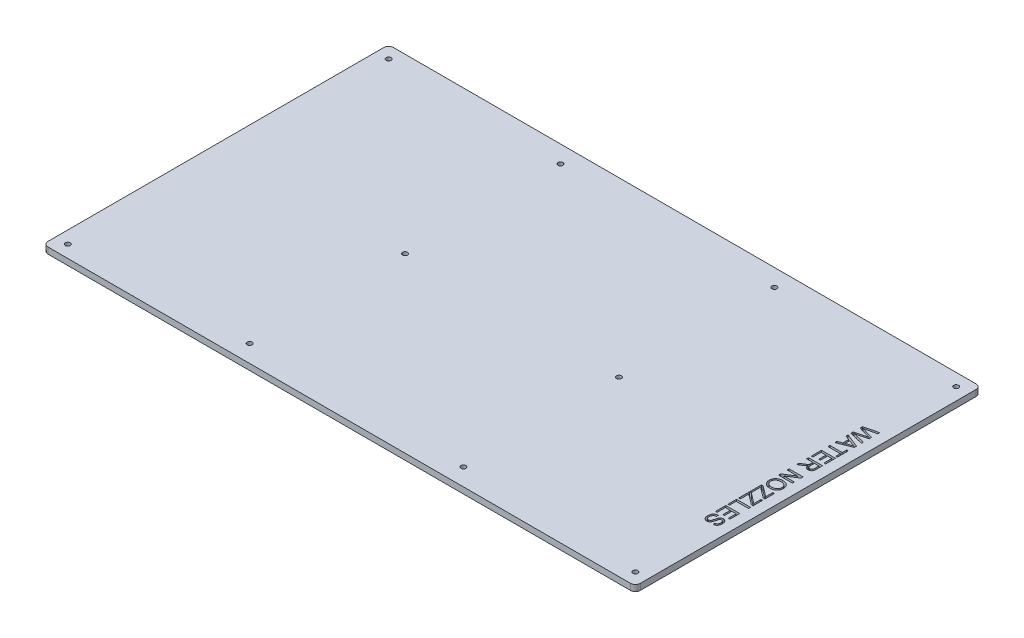
SolidWorks part; units mm, degrees
ref_plane "Front" through (0, 0, 0) normal (0, 0, 1) x (1, 0, 0)
ref_plane "Top" through (0, 0, 0) normal (0, 1, 0) x (1, 0, 0)
ref_plane "Right" through (0, 0, 0) normal (1, 0, 0) x (0, 0, -1)
sketch "Sketch1" plane through (0, 0, 0) normal (0, 1, 0) x (1, 0, 0)
  line L0 (139.7, 88.9) -> (139.7, -88.9) construction
  line L1 (-152.4, 88.9) -> (152.4, 88.9)
  line L2 (-152.4, 88.9) -> (-152.4, -88.9)
  line L3 (-152.4, -88.9) -> (152.4, -88.9)
  line L4 (152.4, 88.9) -> (152.4, -88.9)
  line L5 (-152.4, 88.9) -> (152.4, -88.9) construction
  line L6 (-152.4, -88.9) -> (152.4, 88.9) construction
  circle A0 centre (-55.0291, 80.01) radius 2.4574 construction
  circle A1 centre (-55.0291, 80.01) radius 2.4575 construction
  circle A2 centre (-55.0333, 0) radius 2.4574 construction
  circle A3 centre (-55.0333, 0) radius 2.4575 construction
  circle A4 centre (-55.0291, -80.01) radius 2.4574 construction
  circle A5 centre (-55.0291, -80.01) radius 2.4575 construction
  circle A6 centre (55.0291, -80.01) radius 2.4574 construction
  circle A7 centre (55.0291, -80.01) radius 2.4575 construction
  circle A8 centre (55.0333, 0) radius 2.4574 construction
  circle A9 centre (55.0333, 0) radius 2.4575 construction
  circle A10 centre (55.0291, 80.01) radius 2.4574 construction
  circle A11 centre (55.0291, 80.01) radius 2.4575 construction
  circle A12 centre (-55.0291, 80.01) radius 1.27
  circle A13 centre (-55.0333, 0) radius 1.27
  circle A14 centre (-55.0291, -80.01) radius 1.27
  circle A15 centre (55.0291, -80.01) radius 1.27
  circle A16 centre (55.0333, 0) radius 1.27
  circle A17 centre (55.0291, 80.01) radius 1.27
  circle A18 centre (-146.05, 82.55) radius 1.27
  circle A19 centre (-146.05, -82.55) radius 1.27
  circle A20 centre (146.05, -82.55) radius 1.27
  circle A21 centre (146.05, 82.55) radius 1.27
  point P0 (0, 0)
  dimension "D4" = 2.54
  dimension "D1" = 304.8
  dimension "D2" = 177.8
  dimension "D3" = 12.7
extrude "Boss-Extrude1" add sketch "Sketch1" along normal blind 3.175
sketch "Sketch2" plane through (0, 3.175, 0) normal (0, 1, 0) x (1, 0, 0)
  line L0 (139.7, 88.9) -> (139.7, -88.9) construction
  line L1 (152.4, 88.9) -> (-152.4, 88.9) construction
  line L2 (-152.4, -88.9) -> (152.4, -88.9) construction
  line L3 (152.4, -88.9) -> (152.4, 88.9) construction
  text T0 "WATER NOZZLES" font "Arial" height in points 28
  dimension "D1" = 12.7
extrude "Cut-Extrude1" cut sketch "Sketch2" against normal blind 2.54
fillet "Fillet1" radius 2.54 4 edges at (152.4, 1.5875, -88.9) (152.4, 1.5875, 88.9) (-152.4, 1.5875, 88.9) (-152.4, 1.5875, -88.9)
